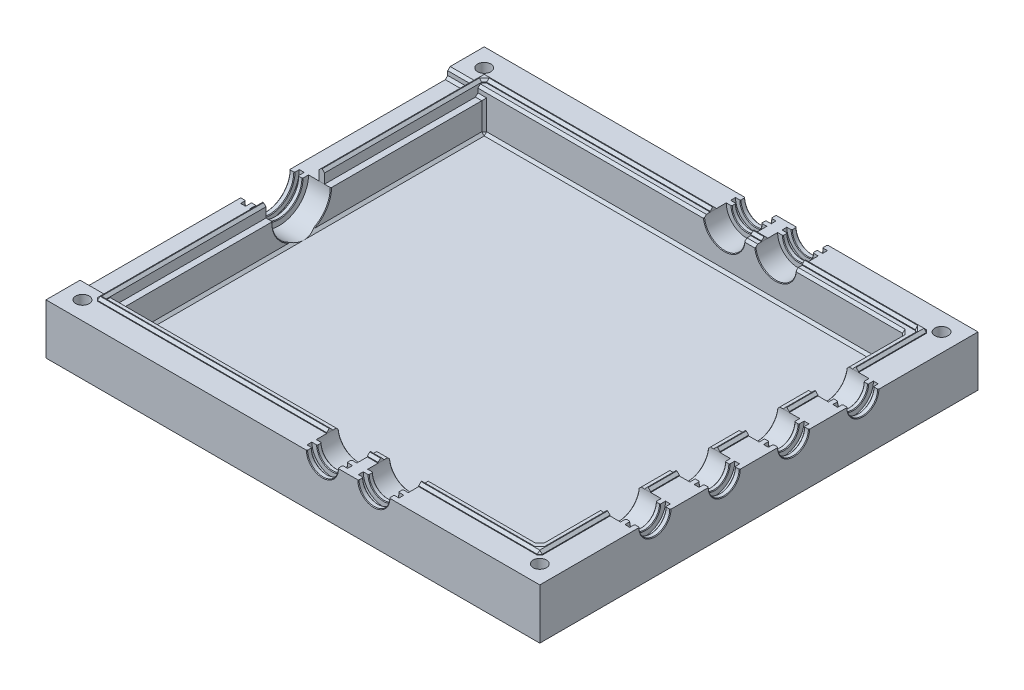
SolidWorks part; units mm, degrees
note: The reader was unsure of these and kept them because the rebuilt part matched: shared geometry of "Sketch2<3>", "Sketch11<3>".
ref_plane "Front Plane" through (0, 0, 0) normal (0, 0, 1) x (1, 0, 0)
ref_plane "Top Plane" through (0, 0, 0) normal (0, 1, 0) x (1, 0, 0)
ref_plane "Right Plane" through (0, 0, 0) normal (1, 0, 0) x (0, 0, -1)
sketch "Sketch1" plane through (0, 0, 0) normal (0, 1, 0) x (1, 0, 0)
  line L1 (0, 0) -> (203.05, 0)
  line L2 (0, 0) -> (0, 180.2)
  line L3 (0, 180.2) -> (203.05, 180.2)
  line L4 (203.05, 0) -> (203.05, 180.2)
  dimension "D1" = 180.2
  dimension "D2" = 203.05
extrude "Boss-Extrude1" add sketch "Sketch1" along normal blind 5
sketch "Sketch2" plane through (0, 5, 0) normal (0, 1, 0) x (1, 0, 0)
  line L0 (15, 15) -> (15, 165.2)
  line L1 (0, 0) -> (203.05, 0)
  line L2 (0, 0) -> (0, 180.2)
  line L3 (0, 180.2) -> (203.05, 180.2)
  line L4 (203.05, 0) -> (203.05, 180.2)
  line L5 (15, 165.2) -> (188.05, 165.2)
  line L6 (188.05, 15) -> (188.05, 165.2)
  line L7 (15, 15) -> (188.05, 15)
  line L8 (15, 165.2) -> (0, 180.2) construction
  line L9 (188.05, 165.2) -> (203.05, 180.2) construction
  line L10 (188.05, 15) -> (203.05, 0) construction
  line L11 (15, 15) -> (0, 0) construction
  line L12 (15, 15) -> (0, 15)
  line L13 (15, 165.2) -> (0, 165.2)
  point P10 (7.5, 172.7)
  point P13 (195.55, 172.7)
  point P14 (195.55, 7.5)
  point P15 (7.5, 7.5)
  line M9 (0, 180.2) -> (0, 0)
  line M10 (0, 0) -> (203.05, 0)
  line M11 (203.05, 0) -> (203.05, 180.2)
  line M12 (203.05, 180.2) -> (0, 180.2)
  dimension "D1" = 15
extrude "Boss-Extrude2" add sketch "Sketch2" along normal blind 12.05 contours L13 L5 L6 L7 L12 L2 M10 M11 M12 M9 | L0 L13 L2 L12
extrude "Boss-Extrude3" add sketch "Sketch2<3>" along normal blind 3.7 from surface contours L13 L5 L6 L7 L12 L2 M10 M11 M12 M9
sketch "Sketch2<3>" plane through (0, 5, 0) normal (0, 1, 0) x (1, 0, 0) same geometry as "Sketch2"
sketch "Sketch7" plane through (0, 20.75, 0) normal (0, 1, 0) x (1, 0, 0)
  point P0 (7.5, 172.7)
  point P1 (195.55, 172.7)
  point P3 (195.55, 7.5)
  point P5 (7.5, 7.5)
hole_wizard "M5 Clearance Hole1" positions "Sketch7" profile "Sketch8" hole size "M5" standard "ANSI Metric"
sketch "Sketch8" plane through (7.5, 20.75, -172.7) normal (1, 0, 0) x (0, 0, 1)
  line L0 (0, 0) -> (0, 22.4024)
  line L1 (0, 22.4024) -> (2.75, 20.75)
  line L2 (2.75, 20.75) -> (2.75, 0)
  line L5 (2.75, 0) -> (0, 0)
  line L10 (0, 22.4024) -> (-2.75, 20.75) construction
  line L11 (0, -6.35) -> (0, 107.95) construction
  dimension "Hole Dia." = 5.5
  dimension "Hole Depth" = 20.75
  dimension "Drill Angle" = 118
sketch "Sketch9" plane through (0, 20.75, 0) normal (0, 1, 0) x (1, 0, 0)
  line L0 (10.1, 170.1) -> (10.1, 10.1)
  line L1 (15, 165.2) -> (188.05, 165.2) construction
  line L2 (15, 165.2) -> (15, 15) construction
  line L3 (15, 15) -> (188.05, 15) construction
  line L4 (188.05, 165.2) -> (188.05, 15) construction
  line L5 (10.1, 10.1) -> (192.95, 10.1)
  line L6 (192.95, 170.1) -> (192.95, 10.1)
  line L7 (10.1, 170.1) -> (192.95, 170.1)
  line L8 (12.4, 167.8) -> (12.4, 12.4)
  line L9 (12.4, 12.4) -> (190.65, 12.4)
  line L10 (190.65, 167.8) -> (190.65, 12.4)
  line L11 (12.4, 167.8) -> (190.65, 167.8)
  dimension "D1" = 4.9
  dimension "D2" = 2.6
extrude "Boss-Extrude4" add sketch "Sketch9" along normal blind 5 from surface at -3.7 starting at face at (7.5, 17.05, -90.1)
chamfer "Chamfer1" distance 1 angle 45 32 edges at (192.95, 22.05, -90.1) (192.95, 21.4, -10.1) (101.525, 22.05, -10.1) (10.1, 21.4, -10.1) (10.1, 22.05, -90.1) (192.95, 21.4, -170.1) (101.525, 22.05, -170.1) (10.1, 21.4, -170.1) (12.4, 22.05, -90.1) (101.525, 22.05, -12.4) (190.65, 21.4, -12.4) (190.65, 22.05, -90.1) (190.65, 21.4, -167.8) (101.525, 22.05, -167.8) (12.4, 21.4, -167.8) (101.525, 5, -15) (188.05, 12.875, -15) (188.05, 5, -90.1) (188.05, 12.875, -165.2) (101.525, 5, -165.2) (15, 5, -90.1) (15, 11.025, -15) (5.05, 20.75, -15) (5.05, 17.05, -15) (5.05, 20.75, -165.2) (5.05, 17.05, -165.2) (13.7, 17.05, -165.2) (100.225, 20.75, -15) (188.05, 20.75, -90.1) (100.225, 20.75, -165.2) (13.7, 17.05, -15) (15, 11.025, -165.2)
sketch "Sketch10" plane through (0, 0, -15) normal (0, 0, -1) x (-1, 0, 0)
  line L0 (-187.05, 20.75) -> (-12.4, 20.75) construction
  line L1 (-113.68, 20.75) -> (-134.8, 20.75) construction
  line L2 (-134.8, 20.75) -> (-203.05, 20.75) construction
  line L3 (-143.15, 20.75) -> (-143.15, 22.05)
  line L4 (-191.95, 22.05) -> (-11.1, 22.05) construction
  line L6 (-126.45, 20.75) -> (-126.45, 22.05)
  line L8 (-143.15, 22.05) -> (-126.45, 22.05)
  line L9 (-122.03, 20.75) -> (-122.03, 22.05)
  line L10 (-122.03, 22.05) -> (-105.33, 22.05)
  line L11 (-105.33, 22.05) -> (-105.33, 20.75)
  arc A0 (-143.15, 20.75) -> (-126.45, 20.75) centre (-134.8, 20.75) ccw
  arc A1 (-122.03, 20.75) -> (-105.33, 20.75) centre (-113.68, 20.75) ccw
  dimension "D2" = 16.7
  dimension "D1" = 21.12
  dimension "D3" = 68.25
extrude "Cut-Extrude1" cut sketch "Sketch10" against normal through all both and the other way through all
sketch "Sketch11" plane through (15, 0, 0) normal (1, 0, 0) x (0, 0, -1)
  line L0 (16, 5) -> (164.2, 5) construction
  line L1 (164.2, 20.75) -> (16, 20.75) construction
  line L2 (75.85, 20.75) -> (104.35, 20.75) construction
  line L3 (75.85, 20.75) -> (0, 20.75) construction
  line L4 (104.35, 20.75) -> (180.2, 20.75) construction
  circle A0 centre (90.1, 17.05) radius 12.05
  circle A1 centre (104.35, 20.75) radius 8.35
  circle A2 centre (75.85, 20.75) radius 8.35
  circle A3 centre (132.85, 20.75) radius 8.35
  circle A5 centre (47.35, 20.75) radius 8.35
  point P8 (90.1, 20.75)
  point P19 (107.73, 19.8003)
  point P22 (0, 0)
  dimension "D1" = 24.1
  dimension "D2" = 16.7
  dimension "D3" = 28.5
  dimension "D4" = 28.5
  dimension "D5" = 28.5
extrude "Cut-Extrude2" cut sketch "Sketch11" against normal through all and the other way up to next contours A0
extrude "Cut-Extrude3" cut sketch "Sketch11<3>" along normal through all from surface at 173.05 contours A2 | A1 | A5 | A3 starting at face at (188.05, 12.875, -90.1)
sketch "Sketch11<3>" plane through (15, 0, 0) normal (1, 0, 0) x (0, 0, -1) same geometry as "Sketch11"
sketch "Sketch12" plane through (203.05, 0, 0) normal (1, 0, 0) x (0, 0, -1)
  line L0 (11.1, 22.05) -> (39.1018, 22.05) construction
  line L1 (67.5, 20.75) -> (84.2, 20.75)
  line L2 (67.5, 20.75) -> (67.5, 22.05)
  line L3 (67.5, 22.05) -> (84.2, 22.05)
  line L4 (84.2, 20.75) -> (84.2, 22.05)
  line L5 (84.0982, 22.05) -> (96.1018, 22.05) construction
  line L6 (84.2, 20.75) -> (96, 20.75) construction
  line L7 (84.2, 20.75) -> (96, 20.75) construction
  line L8 (90.1, 20.75) -> (90.1, 22.05) construction
  line L9 (112.7, 22.05) -> (96, 22.05)
  line L10 (96, 20.75) -> (96, 22.05)
  line L11 (112.7, 20.75) -> (96, 20.75)
  line L12 (112.7, 20.75) -> (112.7, 22.05)
  line L13 (55.7, 20.75) -> (39, 20.75)
  line L14 (55.7, 20.75) -> (55.7, 22.05)
  line L15 (55.7, 22.05) -> (39, 22.05)
  line L16 (39, 20.75) -> (39, 22.05)
  line L17 (141.0982, 22.05) -> (169.1, 22.05) construction
  line L18 (124.5, 20.75) -> (141.2, 20.75)
  line L19 (124.5, 20.75) -> (124.5, 22.05)
  line L20 (124.5, 22.05) -> (141.2, 22.05)
  line L21 (141.2, 20.75) -> (141.2, 22.05)
  arc A0 (39, 20.75) -> (55.7, 20.75) centre (47.35, 20.75) ccw construction
  point P33 (0, 0)
  point P35 (39, 20.75)
extrude "Cut-Extrude4" cut sketch "Sketch12" against normal up to next
sketch "Sketch13" plane through (0, 0, 0) normal (-1, 0, 0) x (0, 0, 1)
  line L1 (-102.15, 17.05) -> (-78.05, 17.05)
  line L2 (-102.15, 17.05) -> (-102.15, 22.05)
  line L3 (-102.15, 22.05) -> (-78.05, 22.05)
  line L4 (-78.05, 17.05) -> (-78.05, 22.05)
  line L5 (-79.1363, 22.05) -> (-11.1, 22.05) construction
extrude "Cut-Extrude5" cut sketch "Sketch13" against normal up to next
sketch "Sketch14" plane through (0, 20.75, 0) normal (0, 1, 0) x (1, 0, 0)
  line L0 (113.68, 180.2) -> (113.68, 165.2) construction
  line L1 (122.03, 180.2) -> (105.33, 180.2) construction
  line L2 (105.3901, 165.2) -> (121.9699, 165.2) construction
  line L3 (105.33, 170.1) -> (105.33, 180.2) construction
  line L4 (105.33, 174.4) -> (107.545, 174.4)
  line L5 (105.33, 174.4) -> (105.33, 176.2)
  line L6 (105.33, 176.2) -> (107.545, 176.2)
  line L7 (107.545, 174.4) -> (107.545, 176.2)
  line L9 (105.33, 178.2) -> (107.33, 178.2)
  line L10 (105.33, 178.2) -> (105.33, 180.2)
  line L11 (105.33, 180.2) -> (107.33, 180.2)
  line L12 (107.33, 178.2) -> (107.33, 180.2)
  dimension "D1" = 2
  dimension "D2" = 2
  dimension "D3" = 6.135
  dimension "D4" = 1.8
  dimension "D5" = 2
revolve "Revolve1" add sketch "Sketch14" angle 180 about L0
ref_plane "Plane1" through (0, 0, -90.1) normal (0, 0, -1) x (-1, 0, 0)
pattern_linear "LPattern1" count 2 spacing 21.12 along (1, 0, 0) of "Revolve1"
mirror "Mirror1" about plane through (0, 0, -90.1) normal (0, 0, -1) of "Revolve1", "LPattern1"
sketch "Sketch15" plane through (0, 20.75, 0) normal (0, 1, 0) x (1, 0, 0)
  line L0 (192.95, 112.7) -> (203.05, 112.7) construction
  line L1 (203.05, 112.7) -> (201.05, 112.7)
  line L2 (203.05, 112.7) -> (203.05, 110.7)
  line L3 (203.05, 110.7) -> (201.05, 110.7)
  line L4 (201.05, 112.7) -> (201.05, 110.7)
  line L5 (199.05, 112.7) -> (197.25, 112.7)
  line L6 (199.05, 112.7) -> (199.05, 110.485)
  line L7 (199.05, 110.485) -> (197.25, 110.485)
  line L8 (197.25, 112.7) -> (197.25, 110.485)
  line L9 (203.05, 104.35) -> (188.05, 104.35) construction
  line L10 (203.05, 96) -> (203.05, 112.7) construction
  line L11 (188.05, 112.6399) -> (188.05, 96.0601) construction
  dimension "D1" = 12.27
  dimension "D2" = 2
  dimension "D3" = 2
  dimension "D4" = 1.8
  dimension "D5" = 2
revolve "Revolve2" add sketch "Sketch15" angle 180 about L9
pattern_linear "LPattern2" count 3 spacing 28.5 along (0, 0, 1) count 2 spacing 28.5 along (0, 0, -1) of "Revolve2"
sketch "Sketch16" plane through (0, 17.05, 0) normal (0, 1, 0) x (1, 0, 0)
  line L0 (16, 90.1) -> (0, 90.1) construction
  line L1 (11.4125, 90.1) -> (-11.4125, 90.1) construction
  line L2 (16, 90.1) -> (16, 16) construction
  line L3 (0, 102.15) -> (0, 78.05) construction
  line L4 (0, 102.15) -> (10.1, 102.15) construction
  line L5 (0, 102.15) -> (2, 102.15)
  line L6 (0, 102.15) -> (0, 100.15)
  line L7 (0, 100.15) -> (2, 100.15)
  line L8 (2, 102.15) -> (2, 100.15)
  line L9 (4, 102.15) -> (5.8, 102.15)
  line L10 (4, 102.15) -> (4, 99.675)
  line L11 (4, 99.675) -> (5.8, 99.675)
  line L12 (5.8, 102.15) -> (5.8, 99.675)
  point P19 (2, 101.15)
  dimension "D1" = 2
  dimension "D2" = 2
  dimension "D3" = 19.15
  dimension "D4" = 2
  dimension "D5" = 1.8
revolve "Revolve3" add sketch "Sketch16" angle 180 about L0
chamfer "Chamfer2" distance 0.25 angle 45 54 edges at (126.465, 20.2491, -14.5009) (105.345, 20.2491, -14.5009) (113.68, 12.4, -165.2) (122.015, 20.2491, -165.6991) (113.68, 12.4, -15) (134.8, 12.4, -165.2) (143.135, 20.2491, -165.6991) (134.8, 12.4, -15) (15, 10.4437, -80.0224) (15, 10.4437, -100.1776) (188.5491, 20.2491, -124.515) (188.05, 12.4, -132.85) (188.5491, 20.2491, -39.015) (188.05, 12.4, -47.35) (188.5491, 20.2491, -96.015) (188.05, 12.4, -104.35) (188.5491, 20.2491, -67.515) (188.05, 12.4, -75.85) (113.68, 14.615, -176.2) (113.68, 14.615, -174.4) (113.68, 14.4, -180.2) (113.68, 14.4, -178.2) (134.8, 14.615, -176.2) (134.8, 14.615, -174.4) (134.8, 14.4, -180.2) (134.8, 14.4, -178.2) (113.68, 14.615, -4) (113.68, 14.615, -5.8) (113.68, 14.4, 0) (113.68, 14.4, -2) (134.8, 14.615, -4) (134.8, 14.615, -5.8) (134.8, 14.4, 0) (134.8, 14.4, -2) (203.05, 14.4, -104.35) (201.05, 14.4, -104.35) (199.05, 14.615, -104.35) (197.25, 14.615, -104.35) (203.05, 14.4, -132.85) (201.05, 14.4, -132.85) (199.05, 14.615, -132.85) (197.25, 14.615, -132.85) (203.05, 14.4, -75.85) (201.05, 14.4, -75.85) (199.05, 14.615, -75.85) (197.25, 14.615, -75.85) (203.05, 14.4, -47.35) (201.05, 14.4, -47.35) (199.05, 14.615, -47.35) (197.25, 14.615, -47.35) (0, 7, -90.1) (2, 7, -90.1) (4, 7.475, -90.1) (5.8, 7.475, -90.1)
